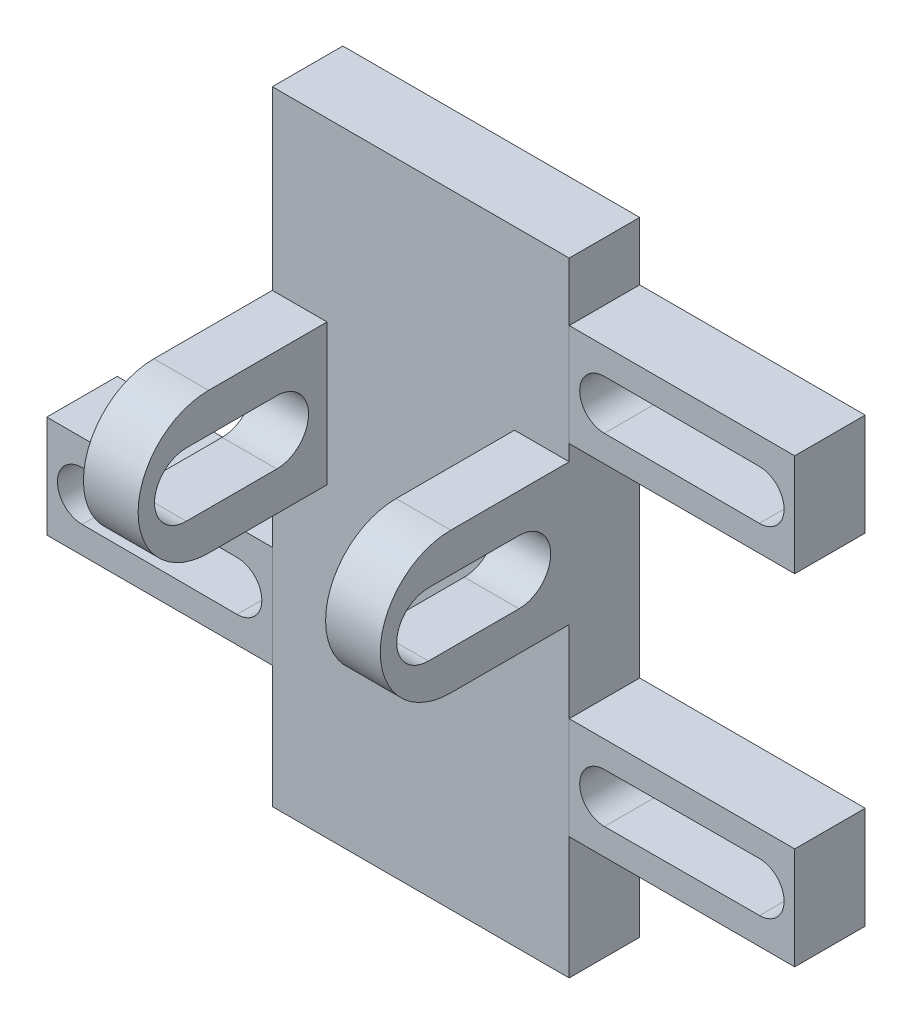
SolidWorks part; units mm, degrees
ref_plane "Front Plane" through (0, 0, 0) normal (0, 0, 1) x (1, 0, 0)
ref_plane "Top Plane" through (0, 0, 0) normal (0, 1, 0) x (1, 0, 0)
ref_plane "Right Plane" through (0, 0, 0) normal (1, 0, 0) x (0, 0, -1)
sketch "Sketch1" plane through (0, 0, 0) normal (0, 0, 1) x (1, 0, 0)
  line L0 (4692.3212, -62.8445) -> (4650.9212, -62.8445) construction
  line L1 (4661.0828, -18.6148) -> (4682.1433, -18.6148)
  line L2 (4661.0828, -18.6148) -> (4661.0828, -62.8445)
  line L3 (4661.0828, -62.8445) -> (4682.1433, -62.8445)
  line L4 (4682.1433, -18.6148) -> (4682.1433, -62.8445)
  line L5 (4661.0828, -27.1456) -> (4658.9212, -27.1456) construction
  line L6 (4658.9212, -12.4285) -> (4658.9212, -50.5381) construction
  line L7 (4682.1433, -34.3161) -> (4684.3037, -34.2412) construction
  line L8 (4684.3037, -50.5381) -> (4684.3037, -12.4285) construction
extrude "Boss-Extrude1" add sketch "Sketch1" along normal blind 5
sketch "Sketch2" plane through (0, 0, 0) normal (0, 0, -1) x (-1, 0, 0)
  line L0 (-4671.6212, -59.6913) -> (-4671.6212, -53.6913) construction
  line L1 (-4664.1212, -59.6913) -> (-4679.1212, -59.6913) construction
  line L2 (-4679.1212, -53.6913) -> (-4664.1212, -53.6913) construction
  line L4 (-4674.1212, -53.8163) -> (-4669.1212, -53.8163)
  line L5 (-4674.1212, -53.8163) -> (-4674.1212, -59.5663)
  line L6 (-4674.1212, -59.5663) -> (-4669.1212, -59.5663)
  line L7 (-4669.1212, -53.8163) -> (-4669.1212, -59.5663)
  line L8 (-4674.1212, -53.8163) -> (-4669.1212, -59.5663) construction
  line L9 (-4674.1212, -59.5663) -> (-4669.1212, -53.8163) construction
  point P6 (-4671.6212, -56.6913)
  dimension "D1" = 5.75
  dimension "D2" = 5
extrude "Boss-Extrude2" add sketch "Sketch2" along normal blind 8
sketch "Sketch4" plane through (4661.0828, 0, 0) normal (-1, 0, 0) x (0, 0, 1)
  line L3 (5, -18.6148) -> (5, -62.8445) construction
  line L4 (13.4005, -31.1292) -> (5, -31.1292)
  line L6 (13.4005, -41.1292) -> (5, -41.1292)
  line L7 (5, -31.1292) -> (5, -41.1292)
  arc A0 (13.4005, -41.1292) -> (13.4005, -31.1292) centre (13.4005, -36.1292) ccw
  dimension "D1" = 5
extrude "Boss-Extrude3" add sketch "Sketch4" against normal blind 3.8801
sketch "Sketch5" plane through (4664.9629, 0, 0) normal (1, 0, 0) x (0, 0, -1)
  line L0 (-14.9864, -36.1292) -> (-8.5634, -36.1292) construction
  line L1 (-14.9864, -33.8792) -> (-8.5634, -33.8792)
  line L2 (-14.9864, -38.3792) -> (-8.5634, -38.3792)
  line L3 (-13.4005, -36.1292) -> (-8.9343, -36.1292) construction
  arc A1 (-14.9864, -33.8792) -> (-14.9864, -38.3792) centre (-14.9864, -36.1292) ccw
  arc A2 (-8.5634, -38.3792) -> (-8.5634, -33.8792) centre (-8.5634, -36.1292) ccw
  point P3 (-11.7749, -36.1292)
  dimension "D1" = 2.25
  dimension "D2" = 1.6257
  dimension "D3" = 4.8372
extrude "Cut-Extrude1" cut sketch "Sketch5" against normal blind 8
ref_plane "Plane1" through (4671.6131, 0, 0) normal (-1, 0, 0) x (0, 0, 1)
mirror "Mirror2" about plane through (4671.6131, 0, 0) normal (-1, 0, 0) of "Cut-Extrude1", "Boss-Extrude3"
sketch "Sketch6" plane through (0, 0, 5) normal (0, 0, 1) x (1, 0, 0)
  line L0 (4688.3131, -48.9131) -> (4688.3131, -52.1631) construction
  line L1 (4682.1433, -46.9131) -> (4698.1433, -46.9131)
  line L2 (4682.1433, -46.9131) -> (4682.1433, -54.1631)
  line L3 (4682.1433, -54.1631) -> (4698.1433, -54.1631)
  line L4 (4698.1433, -46.9131) -> (4698.1433, -54.1631)
  line L5 (4658.9131, -50.5381) -> (4684.2955, -50.5381) construction
  line L6 (4688.3131, -52.1631) -> (4688.3131, -54.1631) construction
  line L7 (4688.3131, -48.9131) -> (4688.3131, -46.9131) construction
  line L8 (4695.6433, -52.2555) -> (4698.1433, -52.2555) construction
  line L9 (4695.6382, -50.5055) -> (4684.6382, -50.5381) construction
  line L10 (4695.6433, -52.2555) -> (4684.6434, -52.2881)
  line L11 (4695.633, -48.7555) -> (4684.633, -48.7881)
  line L12 (4686.6881, -50.5381) -> (4689.9381, -50.5381) construction
  line L13 (4682.1433, -62.8445) -> (4682.1433, -41.1292) construction
  arc A1 (4695.6433, -52.2555) -> (4695.633, -48.7555) centre (4695.6382, -50.5055) ccw
  arc A2 (4684.633, -48.7881) -> (4684.6434, -52.2881) centre (4684.6382, -50.5381) ccw
  circle A3 centre (4688.3131, -50.5381) radius 1.625 construction
  point P18 (4690.1382, -50.5218)
  dimension "D2" = 11
  dimension "D3" = 16
  dimension "D1" = 1.75
  dimension "D4" = 2.5
extrude "Boss-Extrude4" add sketch "Sketch6" against normal blind 5 separate body
ref_plane "Plane2" through (4671.6131, 0, 0) normal (-1, 0, 0) x (0, 0, 1)
mirror "Mirror3" about plane through (4671.6131, 0, 0) normal (-1, 0, 0) of bodies 107
ref_plane "Plane3" through (0, -24.872, 0) normal (0, -1, 0) x (-1, 0, 0)
sketch "Sketch9" plane through (0, 0, 5) normal (0, 0, 1) x (1, 0, 0)
  line L0 (4671.6131, -62.8445) -> (4671.6131, -18.6148) construction
  line L1 (4661.0828, -62.8445) -> (4682.1433, -62.8445) construction
  line L2 (4682.1433, -18.6148) -> (4661.0828, -18.6148) construction
  line L3 (4671.6131, -40.7297) -> (4677.5932, -40.7297) construction
ref_plane "Plane4" through (0, -40.7297, 0) normal (0, -1, 0) x (-1, 0, 0)
sketch "Sketch10" plane through (0, 0, 5) normal (0, 0, 1) x (1, 0, 0)
  line L0 (4654.9131, -26.3852) -> (4654.9131, -50.5381) construction
  line L1 (4654.9131, -38.4617) -> (4652.351, -38.4617) construction
ref_plane "Plane5" through (0, -38.4617, 0) normal (0, -1, 0) x (-1, 0, 0)
mirror "Mirror4" about plane through (0, -38.4617, 0) normal (0, -1, 0) of bodies 109 107
sketch "Sketch11" plane through (0, 0, 5) normal (0, 0, 1) x (1, 0, 0)
  line L1 (4645.0828, -22.7602) -> (4661.0828, -22.7602)
  line L2 (4645.0828, -22.7602) -> (4645.0828, -30.0102)
  line L3 (4645.0828, -30.0102) -> (4661.0828, -30.0102)
  line L4 (4661.0828, -22.7602) -> (4661.0828, -30.0102)
extrude "Cut-Extrude2" cut sketch "Sketch11" against normal up to surface (5 mm away) up to face at (4653.088, -26.4015, 0)
